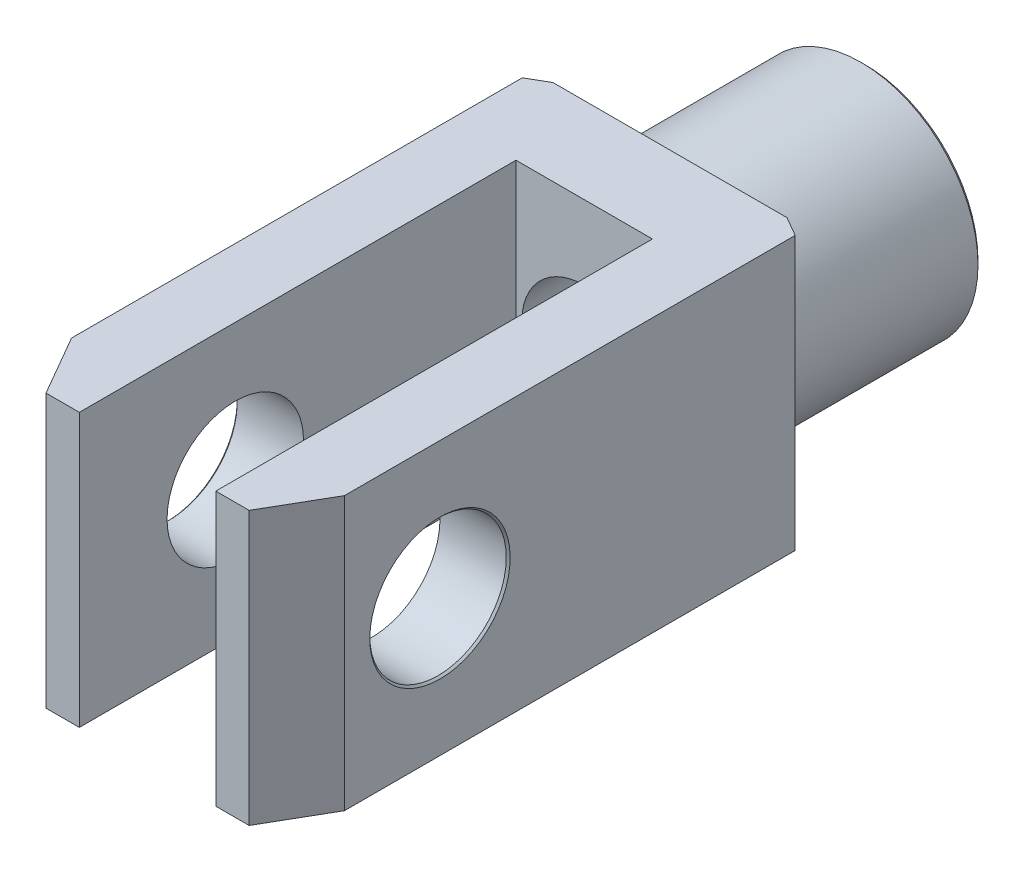
SolidWorks part; units mm, degrees
ref_plane "Front Plane" through (0, 0, 0) normal (0, 0, 1) x (1, 0, 0)
ref_plane "Top Plane" through (0, 0, 0) normal (0, 1, 0) x (1, 0, 0)
ref_plane "Right Plane" through (0, 0, 0) normal (1, 0, 0) x (0, 0, -1)
sketch "Sketch2" plane through (0, 0, 0) normal (0, 0, 1) x (1, 0, 0)
  circle A0 centre (0, 0) radius 30
  dimension "D1" = 60
extrude "Boss-Extrude1" add sketch "Sketch2" along normal blind 50
sketch "Sketch3" plane through (0, 0, 50) normal (0, 0, 1) x (1, 0, 0)
  line L0 (0, 34.3712) -> (0, -35.8936) construction
  line L1 (0, -55) -> (0, 55) construction
  line L2 (-35.0739, 0) -> (35.3081, 0) construction
  line L3 (55, 0) -> (-55, 0) construction
  line L5 (-35, 35) -> (35, 35)
  line L6 (-35, 35) -> (-35, -35)
  line L7 (-35, -35) -> (35, -35)
  line L8 (35, 35) -> (35, -35)
  dimension "D1" = 70
  dimension "D2" = 35
  dimension "D3" = 70
  dimension "D4" = 35
extrude "Boss-Extrude2" add sketch "Sketch3" along normal blind 134
sketch "Sketch4" plane through (0, 0, 184) normal (0, 0, 1) x (1, 0, 0)
  line L0 (0, 40.9195) -> (0, -41.7393) construction
  line L1 (0, -27.5) -> (0, 27.5) construction
  line L2 (-42.1491, 0) -> (45.7014, 0) construction
  line L3 (27.5, 0) -> (-27.5, 0) construction
  line L4 (35, 35) -> (-35, 35) construction
  line L5 (-17.5, 35) -> (17.5, 35)
  line L6 (-17.5, 35) -> (-17.5, -35)
  line L7 (-17.5, -35) -> (17.5, -35)
  line L8 (17.5, 35) -> (17.5, -35)
  line L9 (-35, -35) -> (35, -35) construction
  dimension "D1" = 35
  dimension "D2" = 17.5
extrude "Cut-Extrude1" cut sketch "Sketch4" against normal blind 112
sketch "Sketch5" plane through (0, 0, 0) normal (0, 0, -1) x (-1, 0, 0)
  line L0 (0, 38.2295) -> (0, -39.5332) construction
  line L1 (0, 27.5) -> (0, -27.5) construction
  line L2 (40.4125, 0) -> (-41.3835, 0) construction
  line L3 (27.5, 0) -> (-27.5, 0) construction
  circle A0 centre (0, 0) radius 16
  dimension "D1" = 32
extrude "Cut-Extrude2" cut sketch "Sketch5" against normal blind 72
cosmetic thread "Cosmetic Thread2" parameters "D1"=60, "D2"=36
chamfer "Chamfer1" distance 15.5 angle 30 2 edges at (35, 0, 184) (-35, 0, 184) first distance on face at (35, 0, 117) first distance on face at (-35, 0, 117)
sketch "Sketch6" plane through (35, 0, 0) normal (1, 0, 0) x (0, 0, -1)
  line L0 (-144, 48.4256) -> (-144, -53.4393) construction
  line L1 (-196.4827, 0) -> (19.143, 0) construction
  line L2 (38.5, 0) -> (-38.5, 0) construction
  line L10 (0, 38.5) -> (0, -38.5) construction
  circle A0 centre (-144, 0) radius 17.5
  dimension "D1" = 144
extrude "Cut-Extrude3" cut sketch "Sketch6" against normal blind 70
chamfer "Chamfer2" distance 0.5 angle 45 2 edges at (35, 17.5, 144) (-35, 17.5, 144)
chamfer "Chamfer4" distance 1 angle 45 1 edges at (30, 0, 0)
chamfer "Chamfer6" distance 2 angle 45 1 edges at (-16, 0, 0)
chamfer "Chamfer7" distance 5 angle 30 2 edges at (35, 0, 50) (-35, 0, 50) first distance on face at (0, 0, 50)
